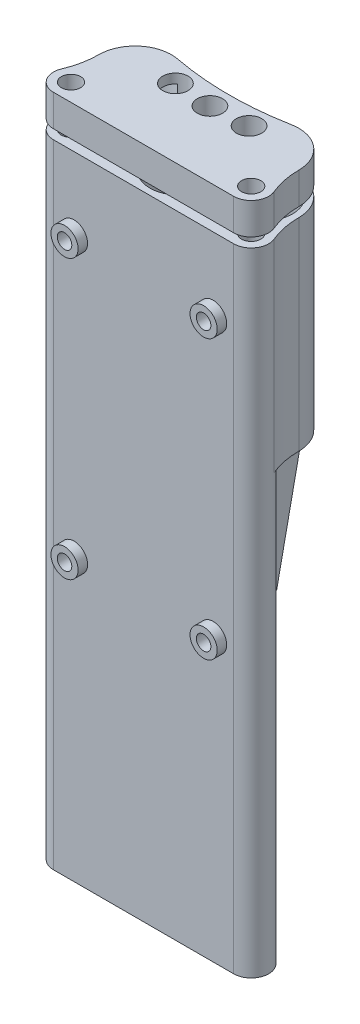
SolidWorks part; units mm, degrees
ref_plane "Front Plane" through (0, 0, 0) normal (0, 0, 1) x (1, 0, 0)
ref_plane "Top Plane" through (0, 0, 0) normal (0, 1, 0) x (1, 0, 0)
ref_plane "Right Plane" through (0, 0, 0) normal (1, 0, 0) x (0, 0, -1)
sketch "Sketch1" plane through (0, 0, 0) normal (0, 1, 0) x (1, 0, 0)
  line L0 (-28.5, 0) -> (28.5, 0) construction
  line L1 (-28.5, 0) -> (28.5, 0) construction
  line L2 (-28.5, 5.55) -> (28.5, 5.55)
  line L3 (-28.5, -5.55) -> (28.5, -5.55)
  circle A0 centre (-28.5, 0) radius 3.05
  circle A1 centre (28.5, 0) radius 3.05
  arc A2 (-28.5, 5.55) -> (-28.5, -5.55) centre (-28.5, 0) ccw
  arc A3 (28.5, -5.55) -> (28.5, 5.55) centre (28.5, 0) ccw
  point P4 (0, 0)
  dimension "D1" = 6.1
  dimension "D2" = 2.5
  dimension "D3" = 57
extrude "Boss-Extrude1" add sketch "Sketch1" along normal mid plane 200
sketch "Sketch2" plane through (0, 0, 0) normal (1, 0, 0) x (0, 0, -1)
  line L0 (5.55, 35.5) -> (5.55, -1.697)
  line L1 (5.55, 100) -> (5.55, -100) construction
  line L2 (5.55, -1.697) -> (8.0456, -1.697)
  line L3 (8.0456, -1.697) -> (15.8164, 35.5)
  line L4 (15.8164, 35.5) -> (5.55, 35.5)
  line L5 (16.6916, 32.3541) -> (10.5567, 2.988) construction
  line L6 (5.55, 100) -> (-5.55, 100) construction
  dimension "D1" = 64.5
  dimension "D2" = 38
  dimension "D3" = 10.2664
extrude "Boss-Extrude2" add sketch "Sketch2" along normal up to vertex (28.5 mm away) and the other way up to vertex (28.5 mm away) up to point (28.5, 100, -5.55) other way up to point (-28.5, 100, -5.55)
sketch "Sketch3" plane through (0, -1.6815, -8.0488) normal (0, -0.2045, -0.9789) x (-1, 0, 0)
  line L0 (-14, 34.0837) -> (-12.3007, 32.25) construction
  line L4 (12.3007, 7.9174) -> (14, 6.0837) construction
  circle A0 centre (-14, 34.0837) radius 1.5
  circle A1 centre (-14, 6.0837) radius 1.5
  circle A2 centre (14, 34.0837) radius 1.5
  circle A3 centre (14, 6.0837) radius 1.5
  circle A4 centre (-14, 34.0837) radius 2.5
  circle A5 centre (14, 34.0837) radius 2.5
  circle A6 centre (14, 6.0837) radius 2.5
  circle A7 centre (-14, 6.0837) radius 2.5
  arc A8 (-15.2495, 34.0495) -> (-13.9658, 35.3332) centre (-14, 34.0837) ccw construction
  arc A9 (-15.2495, 34.0495) -> (-13.9658, 35.3332) centre (-14, 34.0837) ccw construction
  point P25 (-12.8628, 32.5434)
  dimension "D1" = 3
  dimension "D2" = 28
  dimension "D3" = 28
  dimension "D4" = 1
extrude "Boss-Extrude3" add sketch "Sketch3" along normal blind 1.5
chamfer "Chamfer1" distance 0.5 angle 45 4 edges at (14, 6.4141, -11.2725) (-14, 6.4141, -11.2725) (-14, 33.8224, -16.9984) (14, 33.8224, -16.9984)
sketch "Sketch6" plane through (0, 100, 0) normal (0, 1, 0) x (1, 0, 0)
  line L0 (-28.5, -5.55) -> (28.5, -5.55) construction
  line L3 (0, -17.5762) -> (0, 17.5762) construction
  line L4 (-28.5, -5.55) -> (28.5, -5.55)
  arc A0 (-3.9104, 14.6079) -> (3.9104, 14.6079) centre (0, 5.95) ccw
  arc A1 (-14.1587, 19.2894) -> (-10.6457, 12.3022) centre (-20.1375, 11.9067) ccw
  arc A2 (10.6457, 12.3022) -> (14.1587, 19.2894) centre (20.1375, 11.9067) ccw
  circle A4 centre (0, 5.95) radius 11.5 construction
  circle A6 centre (-20.1375, 11.9067) radius 11.5 construction
  circle A7 centre (20.1375, 11.9067) radius 11.5 construction
  circle A8 centre (-28.5, 0) radius 3.05 construction
  circle A10 centre (28.5, 0) radius 3.05 construction
  arc A11 (-31.6375, 11.9067) -> (-33.6123, 2.1604) centre (-56.6757, 11.9067) cw
  arc A12 (-28.5, 5.55) -> (-28.5, -5.55) centre (-28.5, 0) ccw construction
  arc A13 (-31.6375, 11.9067) -> (-17.9882, 23.2041) centre (-20.1375, 11.9067) cw
  arc A14 (31.6375, 11.9067) -> (17.9882, 23.2041) centre (20.1375, 11.9067) ccw
  arc A15 (31.6375, 11.9067) -> (33.6123, 2.1604) centre (56.6757, 11.9067) ccw
  arc A16 (28.5, -5.55) -> (28.5, 5.55) centre (28.5, 0) ccw construction
  arc A17 (-17.9882, 23.2041) -> (17.9882, 23.2041) centre (0, 117.7561) ccw
  arc A18 (-10.6457, 12.3022) -> (-14.1587, 19.2894) centre (-11.6498, 16.1741) ccw
  arc A19 (3.9104, 14.6079) -> (-3.9104, 14.6079) centre (0, 15.45) ccw
  arc A20 (14.1587, 19.2894) -> (10.6457, 12.3022) centre (11.6498, 16.1741) ccw
  circle A21 centre (-11.6498, 16.1741) radius 6 construction
  circle A22 centre (-11.6498, 16.1741) radius 4 construction
  circle A23 centre (-20.1375, 11.9067) radius 9.5 construction
  circle A24 centre (0, 5.95) radius 9.5 construction
  circle A25 centre (20.1375, 11.9067) radius 9.5 construction
  arc A26 (-33.6123, 2.1604) -> (-28.5, -5.55) centre (-28.5, 0) ccw
  arc A27 (33.6123, 2.1604) -> (28.5, -5.55) centre (28.5, 0) cw
  circle A28 centre (-28.5, 0) radius 3.05
  circle A29 centre (28.5, 0) radius 3.05
  line M6 (28.5, 5.55) -> (-28.5, 5.55)
  dimension "D1" = 19
  dimension "D4" = 8
  dimension "D2" = 2
  dimension "D3" = 2
  dimension "D5" = 2
extrude "Boss-Extrude5" add sketch "Sketch6" against normal blind 60
extrude "Cut-Extrude2" cut sketch "Sketch6<2>" against normal up to surface (60 mm away) contours A1 M6 | A0 M6 | A2 M6 region at (20.1375, 100, -4.273) region at (-20.1375, 100, -4.273) region at (0, 100, -1.7011) up to face at (0, 40, -11.9943)
sketch "Sketch6<2>" plane through (0, 100, 0) normal (0, 1, 0) x (1, 0, 0) same geometry as "Sketch6"
sketch "Sketch7" plane through (0, 40, 0) normal (0, -1, 0) x (1, 0, 0)
  line L0 (-28.5, -5.55) -> (28.5, -5.55)
  line L4 (-9.4916, -5.55) -> (-27.1973, -5.55)
  line L7 (-27.1973, -5.55) -> (-28.5, -5.55)
  line L13 (28.5, -5.55) -> (27.1973, -5.55)
  line L14 (13.0776, -5.55) -> (9.4916, -5.55)
  arc A16 (-10.6457, -12.3022) -> (-27.1973, -5.55) centre (-20.1375, -11.9067) ccw
  arc A17 (-14.1587, -19.2894) -> (-10.6457, -12.3022) centre (-11.6498, -16.1741) ccw
  arc A20 (-31.6375, -11.9067) -> (-33.6123, -2.1604) centre (-56.6757, -11.9067) ccw
  arc A21 (-31.6375, -11.9067) -> (-17.9882, -23.2041) centre (-20.1375, -11.9067) ccw
  arc A22 (17.9882, -23.2041) -> (-17.9882, -23.2041) centre (0, -117.7561) ccw
  arc A23 (17.9882, -23.2041) -> (31.6375, -11.9067) centre (20.1375, -11.9067) ccw
  arc A24 (33.6123, -2.1604) -> (31.6375, -11.9067) centre (56.6757, -11.9067) ccw
  arc A26 (14.1587, -19.2894) -> (27.1973, -5.55) centre (20.1375, -11.9067) ccw
  arc A27 (10.6457, -12.3022) -> (14.1587, -19.2894) centre (11.6498, -16.1741) ccw
  arc A30 (-3.9104, -14.6079) -> (3.9104, -14.6079) centre (0, -15.45) ccw
  arc A36 (-31.6375, -11.9067) -> (-33.6123, -2.1604) centre (-56.6757, -11.9067) ccw
  arc A37 (-31.6375, -11.9067) -> (-17.9882, -23.2041) centre (-20.1375, -11.9067) ccw
  arc A38 (17.9882, -23.2041) -> (-17.9882, -23.2041) centre (0, -117.7561) ccw
  arc A39 (17.9882, -23.2041) -> (31.6375, -11.9067) centre (20.1375, -11.9067) ccw
  arc A40 (33.6123, -2.1604) -> (31.6375, -11.9067) centre (56.6757, -11.9067) ccw
  arc A48 (-33.6123, -2.1604) -> (-28.5, -5.55) centre (-28.5, 0) ccw
  arc A49 (-33.6123, -2.1604) -> (-28.5, -5.55) centre (-28.5, 0) ccw
  arc A50 (28.5, -5.55) -> (33.6123, -2.1604) centre (28.5, 0) ccw
  arc A51 (28.5, -5.55) -> (33.6123, -2.1604) centre (28.5, 0) ccw
  arc A52 (-27.1973, -5.55) -> (-14.1587, -19.2894) centre (-20.1375, -11.9067) ccw
  arc A53 (13.0776, -5.55) -> (10.6457, -12.3022) centre (20.1375, -11.9067) ccw
  arc A54 (3.9104, -14.6079) -> (9.4916, -5.55) centre (0, -5.95) ccw
  arc A55 (-9.4916, -5.55) -> (-3.9104, -14.6079) centre (0, -5.95) ccw
  dimension "D1" = 0
extrude "Boss-Extrude6" add sketch "Sketch7" along normal blind 4
extrude "Boss-Extrude7" add sketch "Sketch6<3>" along normal blind 7 from offset 3 separate body
sketch "Sketch6<3>" plane through (0, 100, 0) normal (0, 1, 0) x (1, 0, 0) same geometry as "Sketch6"
sketch "Sketch9" plane through (0, 110, 0) normal (0, 1, 0) x (1, 0, 0)
  line L1 (-28.5, -5.55) -> (28.5, -5.55)
  line L2 (-28.5, -5.55) -> (28.5, -5.55)
  circle A0 centre (-11.6498, 16.1741) radius 4
  circle A1 centre (0, 15.45) radius 4
  circle A2 centre (11.6498, 16.1741) radius 4
  arc A3 (14.1587, 19.2894) -> (10.6457, 12.3022) centre (11.6498, 16.1741) ccw construction
  arc A4 (3.9104, 14.6079) -> (-3.9104, 14.6079) centre (0, 15.45) ccw construction
  arc A5 (-10.6457, 12.3022) -> (-14.1587, 19.2894) centre (-11.6498, 16.1741) ccw construction
  circle A6 centre (28.5, 0) radius 3.05 construction
  arc A7 (-17.9882, 23.2041) -> (-31.6375, 11.9067) centre (-20.1375, 11.9067) ccw
  arc A8 (-33.6123, 2.1604) -> (-31.6375, 11.9067) centre (-56.6757, 11.9067) ccw
  arc A9 (-33.6123, 2.1604) -> (-28.5, -5.55) centre (-28.5, 0) ccw
  arc A10 (28.5, -5.55) -> (33.6123, 2.1604) centre (28.5, 0) ccw
  arc A11 (31.6375, 11.9067) -> (33.6123, 2.1604) centre (56.6757, 11.9067) ccw
  arc A12 (31.6375, 11.9067) -> (17.9882, 23.2041) centre (20.1375, 11.9067) ccw
  arc A13 (-17.9882, 23.2041) -> (17.9882, 23.2041) centre (0, 117.7561) ccw
  arc A14 (-17.9882, 23.2041) -> (-31.6375, 11.9067) centre (-20.1375, 11.9067) ccw
  arc A15 (-33.6123, 2.1604) -> (-31.6375, 11.9067) centre (-56.6757, 11.9067) ccw
  arc A16 (-33.6123, 2.1604) -> (-28.5, -5.55) centre (-28.5, 0) ccw
  arc A17 (28.5, -5.55) -> (33.6123, 2.1604) centre (28.5, 0) ccw
  arc A18 (31.6375, 11.9067) -> (33.6123, 2.1604) centre (56.6757, 11.9067) ccw
  arc A19 (31.6375, 11.9067) -> (17.9882, 23.2041) centre (20.1375, 11.9067) ccw
  arc A20 (-17.9882, 23.2041) -> (17.9882, 23.2041) centre (0, 117.7561) ccw
  circle A21 centre (-28.5, 0) radius 3.05 construction
  circle A22 centre (28.5, 0) radius 3.05
  circle A23 centre (-28.5, 0) radius 3.05
  dimension "D1" = 0
extrude "Boss-Extrude8" add sketch "Sketch9" along normal blind 3
sketch "Sketch4" plane through (0, 0, 5.55) normal (0, 0, 1) x (1, 0, 0)
  line L0 (0, -17.5762) -> (0, 17.5762) construction
  line L1 (-26, 100) -> (26, 100) construction
  line L2 (-26, 100) -> (-26, -15) construction
  line L3 (-26, -15) -> (26, -15) construction
  line L4 (26, 100) -> (26, -15) construction
  line L5 (-28.5, 100) -> (28.5, 100) construction
  line L6 (-22, 77) -> (22, 77) construction
  line L7 (-22, -11) -> (22, -11) construction
  circle A0 centre (-22, 77) radius 2.3
  circle A1 centre (22, 77) radius 2.3
  circle A2 centre (-22, -11) radius 2.3
  circle A3 centre (22, -11) radius 2.3
  circle A4 centre (-22, 77) radius 4.3
  circle A5 centre (22, 77) radius 4.3
  circle A6 centre (-22, -11) radius 4.3
  circle A7 centre (22, -11) radius 4.3
  point P4 (0, 100)
  point P12 (0, 77)
  point P16 (0, -11)
  dimension "D7" = 4.6
  dimension "D1" = 52
  dimension "D2" = 115
  dimension "D3" = 23
  dimension "D4" = 4
  dimension "D5" = 4
  dimension "D6" = 4
  dimension "D8" = 2
extrude "Boss-Extrude4" add sketch "Sketch4" along normal blind 3
extrude "Cut-Extrude1" cut sketch "Sketch4<2>" against normal blind 3 contours A1 | A0 | A3 | A2 region at (-22, 77, 5.55) region at (22, 77, 5.55) region at (-22, -11, 5.55) region at (22, -11, 5.55)
sketch "Sketch4<2>" plane through (0, 0, 5.55) normal (0, 0, 1) x (1, 0, 0) same geometry as "Sketch4"
sketch "Sketch10" plane through (0, 0, -5.55) normal (0, 0, -1) x (-1, 0, 0)
  line L0 (0, 17.5762) -> (0, -17.5762) construction
  line L1 (-24.5, -6.697) -> (24.5, -6.697) construction
  line L2 (-24.5, -6.697) -> (-24.5, -64.697) construction
  line L3 (-24.5, -64.697) -> (24.5, -64.697) construction
  line L4 (24.5, -6.697) -> (24.5, -64.697) construction
  line L5 (-28.5, -1.697) -> (28.5, -1.697) construction
  line L7 (-22.9123, -3.947) -> (-26.0877, -3.947)
  line L8 (-26.0877, -3.947) -> (-27.6754, -6.697)
  line L9 (-27.6754, -6.697) -> (-26.0877, -9.447)
  line L10 (-26.0877, -9.447) -> (-22.9123, -9.447)
  line L11 (-22.9123, -9.447) -> (-21.3246, -6.697)
  line L12 (-21.3246, -6.697) -> (-22.9123, -3.947)
  line L13 (26.0877, -3.947) -> (22.9123, -3.947)
  line L14 (22.9123, -3.947) -> (21.3246, -6.697)
  line L15 (21.3246, -6.697) -> (22.9123, -9.447)
  line L16 (22.9123, -9.447) -> (26.0877, -9.447)
  line L17 (26.0877, -9.447) -> (27.6754, -6.697)
  line L18 (27.6754, -6.697) -> (26.0877, -3.947)
  line L19 (-22.9123, -61.947) -> (-26.0877, -61.947)
  line L20 (-26.0877, -61.947) -> (-27.6754, -64.697)
  line L21 (-27.6754, -64.697) -> (-26.0877, -67.447)
  line L22 (-26.0877, -67.447) -> (-22.9123, -67.447)
  line L23 (-22.9123, -67.447) -> (-21.3246, -64.697)
  line L24 (-21.3246, -64.697) -> (-22.9123, -61.947)
  line L25 (22.9123, -61.947) -> (21.3246, -64.697)
  line L26 (21.3246, -64.697) -> (22.9123, -67.447)
  line L27 (22.9123, -67.447) -> (26.0877, -67.447)
  line L28 (26.0877, -67.447) -> (27.6754, -64.697)
  line L29 (27.6754, -64.697) -> (26.0877, -61.947)
  line L30 (26.0877, -61.947) -> (22.9123, -61.947)
  circle A0 centre (-24.5, -6.697) radius 1.5
  circle A1 centre (24.5, -6.697) radius 1.5
  circle A2 centre (24.5, -64.697) radius 1.5
  circle A3 centre (-24.5, -64.697) radius 1.5
  circle A4 centre (-24.5, -6.697) radius 2.75 construction
  circle A5 centre (24.5, -6.697) radius 2.75 construction
  circle A6 centre (-24.5, -64.697) radius 2.75 construction
  circle A7 centre (24.5, -64.697) radius 2.75 construction
  point P8 (0, -6.697)
  dimension "D1" = 3
  dimension "D2" = 49
  dimension "D3" = 58
  dimension "D4" = 5
  dimension "D5" = 5.5
extrude "Cut-Extrude3" cut sketch "Sketch10" against normal blind 2
extrude "Cut-Extrude4" cut sketch "Sketch10<3>" against normal blind 8 contours A0 | A1 | A3 | A2 region at (24.5, -6.697, -5.55) region at (-24.5, -6.697, -5.55) region at (-24.5, -64.697, -5.55) region at (24.5, -64.697, -5.55)
sketch "Sketch10<3>" plane through (0, 0, -5.55) normal (0, 0, -1) x (-1, 0, 0) same geometry as "Sketch10"
